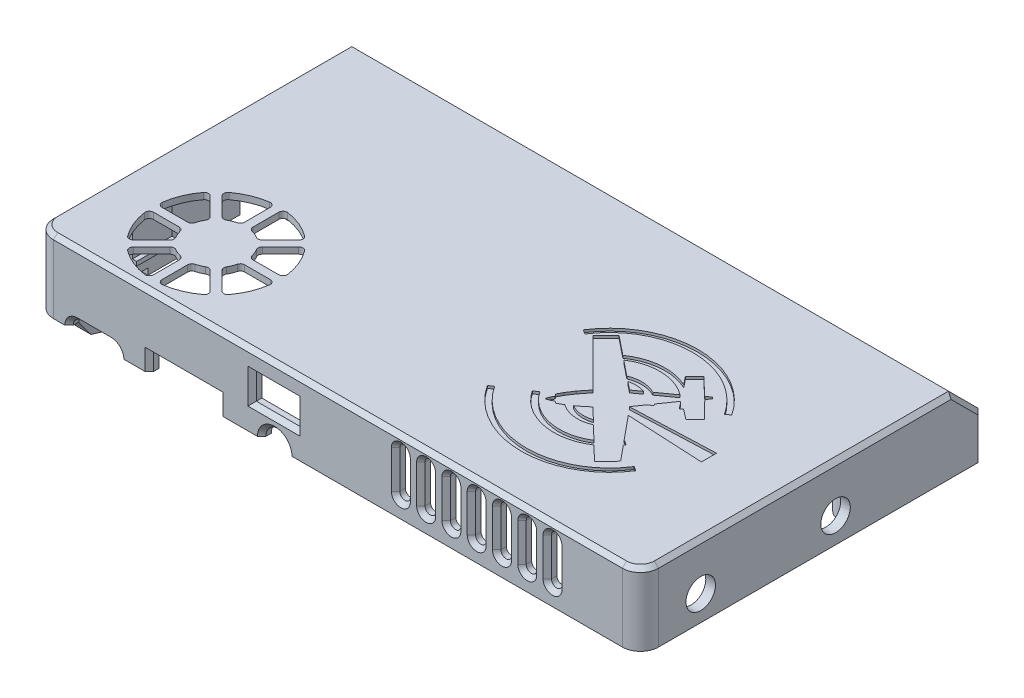
SolidWorks part; units mm, degrees
ref_plane "Front Plane" through (0, 0, 0) normal (0, 0, 1) x (1, 0, 0)
ref_plane "Top Plane" through (0, 0, 0) normal (0, 1, 0) x (1, 0, 0)
ref_plane "Right Plane" through (0, 0, 0) normal (1, 0, 0) x (0, 0, -1)
sketch "Sketch1" plane through (0, 0, 0) normal (0, 1, 0) x (1, 0, 0)
  line L0 (-71.5618, 12.356) -> (65.4382, 12.356) construction
  line L1 (-71.5618, 49.606) -> (65.4382, 49.606)
  line L2 (-71.5618, 49.606) -> (-71.5618, -24.894)
  line L3 (-71.5618, -24.894) -> (65.4382, -24.894)
  line L4 (65.4382, 49.606) -> (65.4382, -24.894)
  line L5 (-60.6618, -24.894) -> (-60.6618, -31.6828) construction
  line L6 (-68.0618, 27.606) -> (-10.0618, 27.606)
  line L7 (-68.0618, 27.606) -> (-68.0618, -21.394)
  line L8 (-68.0618, -21.394) -> (-10.0618, -21.394)
  line L9 (-10.0618, 27.606) -> (-10.0618, -21.394)
  line L10 (-39.5618, -24.894) -> (-39.5618, -31.6828) construction
  line L11 (-18.0618, -24.894) -> (-18.0618, -31.6828) construction
  line L12 (-65.4118, -26.5648) -> (-55.9118, -26.5648) construction
  line L13 (-48.0618, -26.5648) -> (-31.0618, -26.5648) construction
  line L14 (-22.0618, -26.5648) -> (-14.0618, -26.5648) construction
  line L15 (-72.5618, 9.606) -> (-72.5618, -3.394) construction
  line L16 (-71.5618, 12.356) -> (-72.5618, 12.356) construction
  line L17 (-60.6618, -24.894) -> (-60.6618, 40.2849) construction
  dimension "D1" = 137
  dimension "D2" = 74.5
  dimension "D3" = 49
  dimension "D4" = 58
  dimension "D5" = 3.5
  dimension "D6" = 3.5
  dimension "D7" = 10.9
  dimension "D8" = 32
  dimension "D9" = 53.5
  dimension "D10" = 2
  dimension "D11" = 13
  dimension "D12" = 9.5
  dimension "D13" = 17
  dimension "D14" = 8
sketch "Sketch3" plane through (0, 0, 0) normal (0, 1, 0) x (1, 0, 0)
  line L2 (-72.5618, -25.894) -> (66.4382, -25.894) construction
  line L3 (68.7382, -28.194) -> (68.7382, 52.906) construction
  line L4 (68.7382, 52.906) -> (-74.8618, 52.906)
  line L5 (-74.8618, 52.906) -> (-74.8618, -28.194)
  line L6 (-74.8618, -28.194) -> (68.7382, -28.194)
  line L8 (66.4382, 50.606) -> (-72.5618, 50.606)
  line L9 (66.4382, -25.894) -> (66.4382, 50.606)
  line L10 (-72.5618, -25.894) -> (66.4382, -25.894)
  line L11 (-72.5618, 50.606) -> (-72.5618, -25.894)
  line L12 (66.4382, 50.606) -> (-72.5618, 50.606)
  line L13 (66.4382, -25.894) -> (66.4382, 50.606)
  line L14 (-72.5618, -25.894) -> (66.4382, -25.894)
  line L15 (-72.5618, 50.606) -> (-72.5618, -25.894)
  line L16 (-3.0618, 12.356) -> (-3.0618, 52.906) construction
  line L17 (-71.5618, 12.356) -> (65.4382, 12.356) construction
  line L18 (66.4382, -25.894) -> (66.4382, 50.606) construction
  line L20 (-74.8618, 12.356) -> (52.7382, 12.356) construction
  line L22 (-74.8618, -28.194) -> (68.7382, -28.194) construction
  line L23 (68.7382, -28.194) -> (68.7382, 52.906)
  dimension "D1" = 1
  dimension "D2" = 2.3
extrude "Boss-Extrude1" add sketch "Sketch3" along normal blind 17.2
sketch "Sketch5" plane through (0, 0, 0) normal (0, 1, 0) x (1, 0, 0)
  line L1 (-72.5618, 50.606) -> (66.4382, 50.606)
  line L2 (-72.5618, 50.606) -> (-72.5618, -25.894)
  line L3 (-72.5618, -25.894) -> (66.4382, -25.894)
  line L4 (66.4382, 50.606) -> (66.4382, -25.894)
sketch "Sketch11" plane through (0, 0, 28.194) normal (0, 0, 1) x (1, 0, 0)
  line L0 (-74.8618, 17.2) -> (-74.8618, 0) construction
  line L2 (-66.8618, 0) -> (-54.8618, 0)
  line L3 (-66.8618, 0) -> (-66.8618, 2)
  line L4 (-66.8618, 2) -> (-54.8618, 2)
  line L5 (-54.8618, 0) -> (-54.8618, 2)
  line L9 (-47.8118, 4) -> (-31.3118, 4)
  line L10 (-47.8118, 4) -> (-47.8118, 0)
  line L11 (-47.8118, 0) -> (-31.3118, 0)
  line L12 (-31.3118, 4) -> (-31.3118, 0)
  line L14 (-39.5618, 0) -> (-39.528, 10.3) construction
  line L15 (-48.0618, 0) -> (-31.0618, 0) construction
  line L16 (-18.0618, 0) -> (-18.0618, 10.3) construction
  line L17 (-22.0618, 0) -> (-14.0618, 0) construction
  circle A0 centre (-18.0618, 0) radius 3.1
  dimension "D5" = 6.2
  dimension "D1" = 4
  dimension "D2" = 2
  dimension "D3" = 12
  dimension "D4" = 16.5
  dimension "D7" = 8
extrude "Cut-Extrude1" cut sketch "Sketch11" against normal up to next
sketch "Sketch14" plane through (0, 0, 0) normal (0, -1, 0) x (1, 0, 0)
  line L1 (-74.8618, 11.894) -> (-72.5618, 11.894)
  line L2 (-74.8618, 11.894) -> (-74.8618, -18.106)
  line L3 (-74.8618, -18.106) -> (-72.5618, -18.106)
  line L4 (-72.5618, 11.894) -> (-72.5618, -18.106)
  dimension "D1" = 30
extrude "Boss-Extrude6" add sketch "Sketch14" along normal blind 2.8
sketch "Sketch15" plane through (-74.8618, 0, 0) normal (-1, 0, 0) x (0, 0, 1)
  line L0 (11.894, -2.8) -> (-18.106, -2.8) construction
  line L1 (-9.7403, -2.8) -> (3.7597, -2.8)
  line L2 (-9.7403, -2.8) -> (-9.7403, -1.8)
  line L3 (-9.7403, -1.8) -> (3.7597, -1.8)
  line L4 (3.7597, -2.8) -> (3.7597, -1.8)
sketch "Sketch94" plane through (0, -2.8, 0) normal (0, -1, 0) x (1, 0, 0)
  line L0 (-74.8618, -9.7403) -> (-74.8618, 3.7597) construction
  line L1 (-72.5618, 3.7671) -> (-74.8618, 3.7671)
  line L2 (-72.5618, 3.7671) -> (-72.5618, -9.7403)
  line L3 (-72.5618, -9.7403) -> (-74.8618, -9.7403)
  line L4 (-74.8618, 3.7671) -> (-74.8618, -9.7403)
  line L5 (-74.8618, -30.106) -> (-74.8618, -9.7329) construction
extrude "Boss-Extrude11" add sketch "Sketch94" along normal blind 1.5
sketch "Sketch35" plane through (0, 17.2, 0) normal (0, 1, 0) x (1, 0, 0)
  line L1 (-72.5618, 50.606) -> (66.4382, 50.606)
  line L2 (-72.5618, 50.606) -> (-72.5618, -25.894)
  line L3 (-72.5618, -25.894) -> (66.4382, -25.894)
  line L4 (66.4382, 50.606) -> (66.4382, -25.894)
extrude "Boss-Extrude7" add sketch "Sketch35" against normal blind 2
sketch "Sketch36" plane through (0, 17.2, 0) normal (0, 1, 0) x (1, 0, 0)
  line L0 (24.1618, 0.3922) -> (23.0119, -0.3579)
  line L1 (34.6516, 0.4143) -> (35.8046, -0.3309)
  line L2 (24.1474, 7.2037) -> (22.9944, 7.949)
  line L3 (34.6373, 7.2258) -> (35.7871, 7.9759)
  line L4 (45.9489, -6.8877) -> (46.9923, -7.5622)
  line L5 (39.4174, -2.6661) -> (40.5245, -3.3816)
  line L6 (19.409, -2.7082) -> (18.305, -3.4284)
  line L7 (12.8953, -6.9573) -> (11.8548, -7.6361)
  line L8 (12.8501, 14.5058) -> (11.8067, 15.1802)
  line L9 (19.3816, 10.2841) -> (18.2746, 10.9997)
  line L10 (39.3901, 10.3263) -> (40.4941, 11.0465)
  line L11 (45.9037, 14.5754) -> (46.9443, 15.2542)
  line L12 (52.9704, 2.0329) -> (31.2725, 3.1101)
  line L13 (52.9704, 5.6235) -> (31.2725, 4.7515)
  line L14 (52.9704, 2.0329) -> (52.9704, 5.6235)
  line L15 (31.2725, 3.1101) -> (31.2725, 4.7515)
  arc A0 (46.9443, 15.2542) -> (11.8067, 15.1802) centre (29.3995, 3.809) ccw
  arc A1 (45.9037, 14.5754) -> (12.8501, 14.5058) centre (29.3995, 3.809) ccw
  arc A2 (34.6373, 7.2258) -> (24.1474, 7.2037) centre (29.3995, 3.809) ccw
  arc A3 (35.7871, 7.9759) -> (22.9944, 7.949) centre (29.3995, 3.809) ccw
  arc A4 (40.4941, 11.0465) -> (18.2746, 10.9997) centre (29.3995, 3.809) ccw
  arc A5 (39.3901, 10.3263) -> (19.3816, 10.2841) centre (29.3995, 3.809) ccw
  arc A6 (11.8548, -7.6361) -> (46.9923, -7.5622) centre (29.3995, 3.809) ccw
  arc A7 (12.8953, -6.9573) -> (45.9489, -6.8877) centre (29.3995, 3.809) ccw
  arc A8 (18.305, -3.4284) -> (40.5245, -3.3816) centre (29.3995, 3.809) ccw
  arc A9 (19.409, -2.7082) -> (39.4174, -2.6661) centre (29.3995, 3.809) ccw
  arc A10 (23.0119, -0.3579) -> (35.8046, -0.3309) centre (29.3995, 3.809) ccw
  arc A11 (24.1618, 0.3922) -> (34.6516, 0.4143) centre (29.3995, 3.809) ccw
extrude "Cut-Extrude4" cut sketch "Sketch36" against normal blind 0.6
sketch "Sketch37" plane through (0, 17.2, 0) normal (0, 1, 0) x (1, 0, 0)
  line L0 (28.805, 0.4761) -> (40.1826, -10.5566)
  line L1 (40.1826, -10.5566) -> (43.2384, -7.4053)
  line L2 (43.2384, -7.4053) -> (33.0944, 4.8995)
  line L3 (33.0944, 4.8995) -> (38.1664, 12.1985)
  line L4 (38.1664, 12.1985) -> (42.4176, 8.9024)
  line L5 (42.4176, 8.9024) -> (44.5689, 11.121)
  line L6 (44.5689, 11.121) -> (40.5449, 15.2662)
  line L7 (40.5449, 15.2662) -> (41.3442, 16.2971)
  line L8 (41.3442, 16.2971) -> (41.1146, 16.4751)
  line L9 (28.805, 0.4761) -> (26.7077, -1.2529)
  line L10 (26.7077, -1.2529) -> (24.9219, -2.47)
  line L11 (24.9219, -2.47) -> (23.6139, -3.1724)
  line L12 (23.6139, -3.1724) -> (23.1085, -2.8212)
  line L13 (23.1085, -2.8212) -> (22.3443, -3.2316)
  line L14 (22.3443, -3.2316) -> (21.6545, -3.4615)
  line L15 (21.6545, -3.4615) -> (21.4618, -3.4615)
  line L16 (41.1146, 16.4751) -> (21.4618, -3.4615) construction
  line L17 (21.459, -3.2688) -> (21.4618, -3.4615)
  line L18 (21.6791, -2.5758) -> (21.459, -3.2688)
  line L19 (22.0784, -1.8058) -> (21.6791, -2.5758)
  line L20 (21.72, -1.3055) -> (22.0784, -1.8058)
  line L21 (22.4036, 0.0124) -> (21.72, -1.3055)
  line L22 (23.595, 1.8155) -> (22.4036, 0.0124)
  line L23 (25.2938, 3.9374) -> (23.595, 1.8155)
  line L24 (40.9334, 16.7021) -> (41.1146, 16.4751)
  line L25 (39.9141, 15.8881) -> (40.9334, 16.7021)
  line L26 (35.7115, 19.8523) -> (39.9141, 15.8881)
  line L27 (33.524, 17.6694) -> (35.7115, 19.8523)
  line L28 (36.8807, 13.4659) -> (33.524, 17.6694)
  line L29 (29.6552, 8.2897) -> (36.8807, 13.4659)
  line L30 (17.2062, 18.2563) -> (29.6552, 8.2897)
  line L31 (14.099, 15.1556) -> (17.2062, 18.2563)
  line L32 (25.2938, 3.9374) -> (14.099, 15.1556)
extrude "Cut-Extrude5" cut sketch "Sketch37" against normal blind 0.6
sketch "Sketch48" plane through (0, 17.2, 0) normal (0, 1, 0) x (1, 0, 0)
  line L0 (-14.9618, -28.194) -> (68.7382, -28.194) construction
  line L2 (-74.8618, 12.356) -> (-35.5735, 12.356) construction
  line L3 (-74.8618, 52.906) -> (-74.8618, -28.194) construction
  line L4 (68.7382, -28.194) -> (68.7382, 52.906) construction
  circle A0 centre (64.4382, 27.806) radius 4.3
  circle A3 centre (64.4382, -23.894) radius 4.3
  dimension "D1" = 4.3
  dimension "D2" = 56
extrude "Boss-Extrude9" add sketch "Sketch48" against normal up to vertex
sketch "Sketch87" plane through (0, 15.2, 0) normal (0, -1, 0) x (1, 0, 0)
  line L0 (-68.0618, -24.606) -> (-72.5618, -24.606)
  line L1 (-72.5618, -50.606) -> (-72.5618, -18.106) construction
  line L2 (-72.5618, -24.606) -> (-72.5618, -30.606)
  line L3 (-13.0618, -27.606) -> (-13.0618, -30.606)
  line L4 (-65.0618, -30.606) -> (-72.5618, -30.606)
  line L6 (-13.0618, -30.606) -> (-7.0618, -30.606)
  line L7 (-7.0618, -30.606) -> (-7.0618, -27.606)
  line L8 (-13.0618, 21.394) -> (-13.0618, 25.894)
  line L9 (-66.8618, 25.894) -> (-65.1415, 22.0812)
  line L10 (-68.0618, 18.394) -> (-72.5618, 18.394)
  line L11 (-72.5618, 11.894) -> (-72.5618, 25.894) construction
  line L12 (-72.5618, 18.394) -> (-72.5618, 25.894)
  line L13 (-72.5618, 25.894) -> (-66.8618, 25.894)
  line L14 (-65.0618, -27.606) -> (-65.0618, -30.606)
  line L16 (9.9382, 25.894) -> (-54.8618, 25.894) construction
  line L17 (-13.0618, 25.894) -> (-7.0618, 25.894)
  line L18 (-7.0618, 25.894) -> (-7.0618, 21.394)
  arc A0 (-68.0618, 18.394) -> (-65.6141, 23.1287) centre (-68.0618, 21.394) ccw
  arc A1 (-65.0618, -27.606) -> (-68.0618, -24.606) centre (-68.0618, -27.606) ccw
  arc A2 (-13.0618, 21.394) -> (-7.0618, 21.394) centre (-10.0618, 21.394) ccw
  arc A3 (-7.0618, -27.606) -> (-13.0618, -27.606) centre (-10.0618, -27.606) ccw
  arc A4 (-7.0618, -27.606) -> (-13.0618, -27.606) centre (-10.0618, -27.606) ccw
extrude "Boss-Extrude10" add sketch "Sketch87" along normal offset from surface (18.3 mm away) 3.1
fillet "Fillet15" radius 4.3 2 edges at (68.7382, 8.6, 28.194) (-74.8618, 8.6, 28.194)
sketch "Sketch68" plane through (68.7382, 0, 0) normal (1, 0, 0) x (0, 0, -1)
  line L0 (18.106, 6) -> (-13.894, 6) construction
  line L1 (-23.894, 17.2) -> (-23.894, 0) construction
  line L4 (-23.894, 0) -> (52.906, 0) construction
  circle A0 centre (-13.894, 6) radius 3.5
  circle A1 centre (18.106, 6) radius 3.5
  dimension "D1" = 32
  dimension "D2" = 10
  dimension "D3" = 6
extrude "Cut-Extrude19" cut sketch "Sketch68" against normal up to next
sketch "Sketch81" plane through (0, 0, 28.194) normal (0, 0, 1) x (1, 0, 0)
  line L0 (47.876, 4.6038) -> (47.876, 13.6038) construction
  line L1 (46.626, 4.6038) -> (46.626, 13.6038)
  line L2 (49.126, 4.6038) -> (49.126, 13.6038)
  line L3 (41.876, 4.6038) -> (41.876, 13.6038) construction
  line L4 (40.626, 4.6038) -> (40.626, 13.6038)
  line L5 (43.126, 4.6038) -> (43.126, 13.6038)
  line L6 (35.876, 4.6038) -> (35.876, 13.6038) construction
  line L7 (34.626, 4.6038) -> (34.626, 13.6038)
  line L8 (37.126, 4.6038) -> (37.126, 13.6038)
  line L9 (29.876, 4.6038) -> (29.876, 13.6038) construction
  line L10 (28.626, 4.6038) -> (28.626, 13.6038)
  line L11 (31.126, 4.6038) -> (31.126, 13.6038)
  line L12 (23.876, 4.6038) -> (23.876, 13.6038) construction
  line L13 (22.626, 4.6038) -> (22.626, 13.6038)
  line L14 (25.126, 4.6038) -> (25.126, 13.6038)
  line L15 (17.876, 4.6038) -> (17.876, 13.6038) construction
  line L16 (16.626, 4.6038) -> (16.626, 13.6038)
  line L17 (19.126, 4.6038) -> (19.126, 13.6038)
  line L18 (11.876, 4.6038) -> (11.876, 13.6038) construction
  line L19 (10.626, 4.6038) -> (10.626, 13.6038)
  line L20 (13.126, 4.6038) -> (13.126, 13.6038)
  arc A0 (46.626, 4.6038) -> (49.126, 4.6038) centre (47.876, 4.6038) ccw
  arc A1 (49.126, 13.6038) -> (46.626, 13.6038) centre (47.876, 13.6038) ccw
  arc A2 (40.626, 4.6038) -> (43.126, 4.6038) centre (41.876, 4.6038) ccw
  arc A3 (43.126, 13.6038) -> (40.626, 13.6038) centre (41.876, 13.6038) ccw
  arc A4 (34.626, 4.6038) -> (37.126, 4.6038) centre (35.876, 4.6038) ccw
  arc A5 (37.126, 13.6038) -> (34.626, 13.6038) centre (35.876, 13.6038) ccw
  arc A6 (28.626, 4.6038) -> (31.126, 4.6038) centre (29.876, 4.6038) ccw
  arc A7 (31.126, 13.6038) -> (28.626, 13.6038) centre (29.876, 13.6038) ccw
  arc A8 (22.626, 4.6038) -> (25.126, 4.6038) centre (23.876, 4.6038) ccw
  arc A9 (25.126, 13.6038) -> (22.626, 13.6038) centre (23.876, 13.6038) ccw
  arc A10 (16.626, 4.6038) -> (19.126, 4.6038) centre (17.876, 4.6038) ccw
  arc A11 (19.126, 13.6038) -> (16.626, 13.6038) centre (17.876, 13.6038) ccw
  arc A12 (10.626, 4.6038) -> (13.126, 4.6038) centre (11.876, 4.6038) ccw
  arc A13 (13.126, 13.6038) -> (10.626, 13.6038) centre (11.876, 13.6038) ccw
  point P2 (47.876, 9.1038)
  point P11 (41.876, 9.1038)
  point P18 (35.876, 9.1038)
  point P25 (29.876, 9.1038)
  point P32 (23.876, 9.1038)
  point P39 (17.876, 9.1038)
  point P44 (11.876, 9.1038)
  dimension "D1" = 7
extrude "Cut-Extrude20" cut sketch "Sketch81" against normal up to surface (2.3 mm away) up to face at (-38.6618, 3.7917, 25.894)
fillet "Fillet24" radius 2 1 edges at (60.6317, 7.6, 25.894)
fillet "Fillet25" radius 2 1 edges at (-54.8618, 2, 27.044)
fillet "Fillet26" radius 2 1 edges at (-66.8618, 2, 27.044)
chamfer "Chamfer1" distance 1 angle 45 7 edges at (-18.0618, 3.1, 28.194) (-31.3118, 2, 28.194) (-39.5618, 4, 28.194) (-47.8118, 2, 28.194) (-55.4476, 1.4142, 28.194) (-60.8618, 2, 28.194) (-66.276, 1.4142, 28.194)
fillet "Fillet51" radius 3 1 edges at (-72.5618, -1.55, 25.894)
chamfer "Chamfer3" distance 2 angle 56 5 edges at (-68.2118, -3.1, 25.894) (-71.6831, -3.1, 25.0153) (-72.5618, -3.1, 20.644) (-72.5618, -3.1, -27.606) (-10.0618, -3.1, 25.894)
hole_wizard "Ø2.3 (2.3) Diameter Hole2" positions "Sketch91" profile "Sketch90" hole size "Ø2.3" standard "ANSI Metric"
sketch "Sketch91" plane through (0, 0, 0) normal (0, -1, 0) x (-1, 0, 0)
  point P0 (-64.4382, -23.894)
  point P7 (-64.4382, 27.806)
sketch "Sketch90" plane through (64.4382, 0, 23.894) normal (1, 0, 0) x (0, 0, -1)
  line L0 (0, 0) -> (0, 12)
  line L1 (0, 12) -> (1.15, 12)
  line L2 (1.15, 12) -> (1.15, 0)
  line L5 (1.15, 0) -> (0, 0)
  line L10 (0, 12) -> (-1.15, 12) construction
  line L11 (0, -6.35) -> (0, 107.95) construction
  dimension "Hole Dia." = 2.3
  dimension "Hole Depth" = 12
  dimension "Drill Angle" = 180
hole_wizard "Ø2.3 (2.3) Diameter Hole1" positions "Sketch93" profile "Sketch92" hole size "Ø2.3" standard "ANSI Metric"
sketch "Sketch93" plane through (0, -3.1, 0) normal (0, -1, 0) x (-1, 0, 0)
  point P0 (68.0618, -21.394)
  point P4 (68.0618, 27.606)
  point P7 (10.0618, 27.606)
  point P11 (10.0618, -21.394)
sketch "Sketch92" plane through (-68.0618, -3.1, 21.394) normal (1, 0, 0) x (0, 0, -1)
  line L0 (0, 0) -> (0, 13)
  line L1 (0, 13) -> (1.15, 13)
  line L2 (1.15, 13) -> (1.15, 0)
  line L5 (1.15, 0) -> (0, 0)
  line L10 (0, 13) -> (-1.15, 13) construction
  line L11 (0, -6.35) -> (0, 107.95) construction
  dimension "Hole Dia." = 2.3
  dimension "Hole Depth" = 13
  dimension "Drill Angle" = 180
chamfer "Chamfer4" distance 1 angle 45 1 edges at (-74.8618, -4.3, -2.9866)
sketch "Sketch95" plane through (-74.8618, 0, 0) normal (-1, 0, 0) x (0, 0, 1)
  line L0 (-18.606, 14.2331) -> (-18.606, 8.1669) construction
  line L1 (-25.5774, 11.2) -> (-11.6346, 11.2) construction
  line L2 (-24.606, -3.1) -> (-30.606, -3.1) construction
  line L3 (-24.606, -0.1349) -> (-24.606, -3.1) construction
  line L7 (-23.606, 13.2) -> (-13.606, 13.2)
  line L8 (-23.606, 13.2) -> (-23.606, 9.2)
  line L9 (-23.606, 9.2) -> (-13.606, 9.2)
  line L10 (-13.606, 13.2) -> (-13.606, 9.2)
  line L11 (-23.606, 13.2) -> (-13.606, 9.2) construction
  line L12 (-23.606, 9.2) -> (-13.606, 13.2) construction
  point P6 (-18.606, 11.2)
  dimension "D1" = 14.3
  dimension "D2" = 6
  dimension "D3" = 10
  dimension "D4" = 4
extrude "Cut-Extrude21" cut sketch "Sketch95" against normal up to next
fillet "Fillet52" radius 1 4 edges at (-73.7118, 9.2, -23.606) (-73.7118, 9.2, -13.606) (-73.7118, 13.2, -13.606) (-73.7118, 13.2, -23.606)
chamfer "Chamfer5" distance 1 angle 45 8 edges at (-74.8618, 13.2, -18.606) (-74.8618, 12.9071, -23.3131) (-74.8618, 12.9071, -13.8989) (-74.8618, 11.2, -23.606) (-74.8618, 11.2, -13.606) (-74.8618, 9.4929, -23.3131) (-74.8618, 9.4929, -13.8989) (-74.8618, 9.2, -18.606)
sketch "Sketch96" plane through (0, 15.2, 0) normal (0, -1, 0) x (1, 0, 0)
  line L0 (-31.3118, 25.894) -> (-47.8118, 25.894) construction
  line L1 (-64.7549, -4.606) -> (-34.2549, -4.606)
  line L2 (-64.7549, -4.606) -> (-64.7549, 25.894)
  line L3 (-64.7549, 25.894) -> (-34.2549, 25.894)
  line L4 (-34.2549, -4.606) -> (-34.2549, 25.894)
  dimension "D1" = 30.5
  dimension "D2" = 30.5
extrude "Cut-Extrude22" cut sketch "Sketch96" against normal blind 0.5
sketch "Sketch97" plane through (0, 15.7, 0) normal (0, -1, 0) x (1, 0, 0)
  line L1 (-48.5049, 18.39) -> (-48.5049, 24.5004)
  line L2 (-50.5049, 18.39) -> (-50.5049, 24.5004)
  line L5 (-43.3206, 15.4141) -> (-38.9999, 19.7349)
  line L6 (-44.7348, 16.8283) -> (-40.4141, 21.1491)
  line L7 (-41.759, 9.644) -> (-35.6485, 9.644)
  line L8 (-41.759, 11.644) -> (-35.6485, 11.644)
  line L9 (-44.7348, 4.4597) -> (-40.4141, 0.1389)
  line L10 (-43.3206, 5.8739) -> (-38.9999, 1.5532)
  line L11 (-50.5049, 2.898) -> (-50.5049, -3.2124)
  line L12 (-48.5049, 2.898) -> (-48.5049, -3.2124)
  line L13 (-55.6893, 5.8739) -> (-60.01, 1.5532)
  line L14 (-54.275, 4.4597) -> (-58.5958, 0.1389)
  line L15 (-57.2509, 11.644) -> (-63.3613, 11.644)
  line L16 (-57.2509, 9.644) -> (-63.3613, 9.644)
  line L17 (-54.275, 16.8283) -> (-58.5958, 21.1491)
  line L18 (-55.6893, 15.4141) -> (-60.01, 19.7349)
  arc A0 (-61.518, 19.6266) -> (-64.3511, 12.7869) centre (-49.5049, 10.644) ccw
  arc A1 (-55.5349, 14.1991) -> (-56.2826, 12.394) centre (-49.5049, 10.644) ccw
  arc A2 (-56.2826, 8.894) -> (-55.5349, 7.0889) centre (-49.5049, 10.644) ccw
  arc A3 (-64.3511, 8.5011) -> (-61.518, 1.6614) centre (-49.5049, 10.644) ccw
  arc A4 (-58.4875, -1.369) -> (-51.6478, -4.2021) centre (-49.5049, 10.644) ccw
  arc A5 (-53.0601, 4.614) -> (-51.2549, 3.8663) centre (-49.5049, 10.644) ccw
  arc A6 (-47.7549, 3.8663) -> (-45.9498, 4.614) centre (-49.5049, 10.644) ccw
  arc A7 (-47.3621, -4.2021) -> (-40.5223, -1.369) centre (-49.5049, 10.644) ccw
  arc A8 (-37.4919, 1.6614) -> (-34.6588, 8.5011) centre (-49.5049, 10.644) ccw
  arc A9 (-43.4749, 7.0889) -> (-42.7272, 8.894) centre (-49.5049, 10.644) ccw
  arc A10 (-42.7272, 12.394) -> (-43.4749, 14.1991) centre (-49.5049, 10.644) ccw
  arc A11 (-34.6588, 12.7869) -> (-37.4919, 19.6266) centre (-49.5049, 10.644) ccw
  arc A12 (-40.5223, 22.657) -> (-47.3621, 25.4902) centre (-49.5049, 10.644) ccw
  arc A13 (-45.9498, 16.674) -> (-47.7549, 17.4217) centre (-49.5049, 10.644) ccw
  arc A14 (-51.2549, 17.4217) -> (-53.0601, 16.674) centre (-49.5049, 10.644) ccw
  arc A15 (-51.6478, 25.4902) -> (-58.4875, 22.657) centre (-49.5049, 10.644) ccw
  arc A16 (-56.2826, 8.894) -> (-57.2509, 9.644) centre (-57.2509, 8.644) ccw
  arc A17 (-64.3511, 8.5011) -> (-63.3613, 9.644) centre (-63.3613, 8.644) cw
  arc A18 (-61.518, 1.6614) -> (-60.01, 1.5532) centre (-60.7171, 2.2603) ccw
  arc A19 (-55.6893, 5.8739) -> (-55.5349, 7.0889) centre (-56.3964, 6.581) ccw
  arc A20 (-50.5049, 2.898) -> (-51.2549, 3.8663) centre (-51.5049, 2.898) ccw
  arc A21 (-54.275, 4.4597) -> (-53.0601, 4.614) centre (-53.5679, 3.7526) cw
  arc A22 (-58.4875, -1.369) -> (-58.5958, 0.1389) centre (-57.8887, -0.5682) cw
  arc A23 (-51.6478, -4.2021) -> (-50.5049, -3.2124) centre (-51.5049, -3.2124) ccw
  arc A24 (-47.3621, -4.2021) -> (-48.5049, -3.2124) centre (-47.5049, -3.2124) cw
  arc A25 (-40.5223, -1.369) -> (-40.4141, 0.1389) centre (-41.1212, -0.5682) ccw
  arc A26 (-47.7549, 3.8663) -> (-48.5049, 2.898) centre (-47.5049, 2.898) ccw
  arc A27 (-44.7348, 4.4597) -> (-45.9498, 4.614) centre (-45.4419, 3.7526) ccw
  arc A28 (-38.9999, 1.5532) -> (-37.4919, 1.6614) centre (-38.2928, 2.2603) ccw
  arc A29 (-43.3206, 5.8739) -> (-43.4749, 7.0889) centre (-42.6135, 6.581) cw
  arc A30 (-41.759, 9.644) -> (-42.7272, 8.894) centre (-41.759, 8.644) ccw
  arc A31 (-34.6588, 8.5011) -> (-35.6485, 9.644) centre (-35.6485, 8.644) ccw
  arc A32 (-35.6485, 11.644) -> (-34.6588, 12.7869) centre (-35.6485, 12.644) ccw
  arc A33 (-42.7272, 12.394) -> (-41.759, 11.644) centre (-41.759, 12.644) ccw
  arc A34 (-43.4749, 14.1991) -> (-43.3206, 15.4141) centre (-42.6135, 14.707) cw
  arc A35 (-37.4919, 19.6266) -> (-38.9999, 19.7349) centre (-38.2928, 19.0278) ccw
  arc A36 (-40.4141, 21.1491) -> (-40.5223, 22.657) centre (-41.1212, 21.8562) ccw
  arc A37 (-44.7348, 16.8283) -> (-45.9498, 16.674) centre (-45.4419, 17.5354) cw
  arc A38 (-47.7549, 17.4217) -> (-48.5049, 18.39) centre (-47.5049, 18.39) cw
  arc A39 (-48.5049, 24.5004) -> (-47.3621, 25.4902) centre (-47.5049, 24.5004) cw
  arc A40 (-50.5049, 24.5004) -> (-51.6478, 25.4902) centre (-51.5049, 24.5004) ccw
  arc A41 (-51.2549, 17.4217) -> (-50.5049, 18.39) centre (-51.5049, 18.39) ccw
  arc A42 (-53.0601, 16.674) -> (-54.275, 16.8283) centre (-53.5679, 17.5354) cw
  arc A43 (-58.5958, 21.1491) -> (-58.4875, 22.657) centre (-57.8887, 21.8562) cw
  arc A44 (-60.01, 19.7349) -> (-61.518, 19.6266) centre (-60.7171, 19.0278) ccw
  arc A45 (-55.5349, 14.1991) -> (-55.6893, 15.4141) centre (-56.3964, 14.707) ccw
  arc A46 (-57.2509, 11.644) -> (-56.2826, 12.394) centre (-57.2509, 12.644) ccw
  arc A47 (-63.3613, 11.644) -> (-64.3511, 12.7869) centre (-63.3613, 12.644) cw
  point P43 (-49.5049, 10.644)
  point P80 (-48.5049, 17.5722)
  point P83 (-48.5049, 25.6106)
  point P86 (-50.5049, 25.6106)
  point P89 (-50.5049, 17.5722)
  dimension "D1" = 1
  dimension "D3" = 8
extrude "Cut-Extrude23" cut sketch "Sketch97" against normal up to next
sketch "Sketch98" plane through (0, 15.2, 0) normal (0, -1, 0) x (1, 0, 0)
  line L0 (-64.7549, 25.894) -> (-64.7549, -4.606) construction
  line L1 (-64.7549, 15.2653) -> (-66.7549, 15.2653)
  line L2 (-64.7549, 15.2653) -> (-64.7549, 5.8822)
  line L3 (-64.7549, 5.8822) -> (-66.7549, 5.8822)
  line L4 (-66.7549, 15.2653) -> (-66.7549, 5.8822)
  line L5 (-32.2549, 15.3356) -> (-34.2549, 15.3356)
  line L6 (-32.2549, 5.9524) -> (-34.2549, 5.9524)
  line L7 (-32.2549, 15.3356) -> (-32.2549, 5.9524)
  line L8 (-34.2549, 15.3356) -> (-34.2549, 5.9524)
  dimension "D1" = 2
  dimension "D2" = 2
extrude "Boss-Extrude12" add sketch "Sketch98" along normal blind 7.5
sketch "Sketch100" plane through (-64.7549, 0, 0) normal (1, 0, 0) x (0, 0, -1)
  line L0 (-5.8822, 7.7) -> (-5.8822, 15.2) construction
  line L1 (-15.2653, 7.7) -> (-5.8822, 7.7)
  line L2 (-15.2653, 7.7) -> (-15.2653, 8.7)
  line L3 (-15.2653, 8.7) -> (-5.8822, 8.7)
  line L4 (-5.8822, 7.7) -> (-5.8822, 8.7)
  dimension "D1" = 1
extrude "Boss-Extrude13" add sketch "Sketch100" along normal blind 1
sketch "Sketch101" plane through (-34.2549, 0, 0) normal (-1, 0, 0) x (0, 0, 1)
  line L0 (5.9524, 7.7) -> (5.9524, 15.2) construction
  line L1 (15.3356, 7.7) -> (5.9524, 7.7)
  line L2 (15.3356, 7.7) -> (15.3356, 8.7)
  line L3 (15.3356, 8.7) -> (5.9524, 8.7)
  line L4 (5.9524, 7.7) -> (5.9524, 8.7)
  dimension "D1" = 1
extrude "Boss-Extrude14" add sketch "Sketch101" along normal blind 1
sketch "Sketch103" plane through (0, 15.2, 0) normal (0, -1, 0) x (1, 0, 0)
  line L0 (66.4382, 20.0874) -> (66.4382, -23.9994) construction
  line L1 (-72.5618, -30.606) -> (66.4382, -30.606)
  line L2 (-72.5618, -30.606) -> (-72.5618, -32.106)
  line L3 (-72.5618, -32.106) -> (66.4382, -32.106)
  line L4 (66.4382, -30.606) -> (66.4382, -32.106)
  dimension "D1" = 1.5
extrude "Boss-Extrude24" add sketch "Sketch103" along normal up to surface (15.2 mm away) up to face at (-71.063, 0, 22.5852)
chamfer "Chamfer6" distance 1 angle 45 28 edges at (49.126, 9.1038, 28.194) (47.876, 14.8538, 28.194) (47.876, 3.3538, 28.194) (46.626, 9.1038, 28.194) (43.126, 9.1038, 28.194) (41.876, 14.8538, 28.194) (41.876, 3.3538, 28.194) (40.626, 9.1038, 28.194) (37.126, 9.1038, 28.194) (35.876, 14.8538, 28.194) (35.876, 3.3538, 28.194) (34.626, 9.1038, 28.194) (31.126, 9.1038, 28.194) (29.876, 14.8538, 28.194) (29.876, 3.3538, 28.194) (28.626, 9.1038, 28.194) (25.126, 9.1038, 28.194) (23.876, 14.8538, 28.194) (23.876, 3.3538, 28.194) (22.626, 9.1038, 28.194) (19.126, 9.1038, 28.194) (17.876, 14.8538, 28.194) (17.876, 3.3538, 28.194) (16.626, 9.1038, 28.194) (13.126, 9.1038, 28.194) (11.876, 14.8538, 28.194) (11.876, 3.3538, 28.194) (10.626, 9.1038, 28.194)
chamfer "Chamfer7" distance 1 angle 45 5 edges at (68.7382, 17.2, -14.506) (67.4788, 17.2, 26.9346) (-3.0618, 17.2, 28.194) (-73.6023, 17.2, 26.9346) (-74.8618, 17.2, -14.506)
sketch "Sketch105" plane through (0, 0, 0) normal (0, -1, 0) x (1, 0, 0)
  line L0 (-3.0618, -32.106) -> (-3.0618, -50.606) construction
  line L1 (-72.5618, -32.106) -> (66.4382, -32.106) construction
  line L3 (-4.0618, -32.106) -> (-4.0618, -50.606)
  line L4 (-2.0618, -32.106) -> (-2.0618, -50.606)
  line L5 (-4.0618, -32.106) -> (-2.0618, -32.106)
  line L6 (-4.0618, -50.606) -> (-2.0618, -50.606)
  dimension "D1" = 1
  dimension "D2" = 1
extrude "Boss-Extrude25" add sketch "Sketch105" against normal up to surface (15.2 mm away) up to face at (-3.0618, 15.2, -41.356)
sketch "Sketch106" plane through (0, 0, 0) normal (0, -1, 0) x (1, 0, 0)
  line L0 (-72.5618, -32.106) -> (-4.0618, -32.106) construction
  line L1 (-71.189, -32.106) -> (-70.189, -32.106)
  line L2 (-71.189, -32.106) -> (-71.189, -50.606)
  line L3 (-71.189, -50.606) -> (-70.189, -50.606)
  line L4 (-70.189, -32.106) -> (-70.189, -50.606)
  line L5 (-4.0618, -50.606) -> (-72.5618, -50.606) construction
  line L7 (-70.189, -38.0184) -> (-69.0618, -38.0184)
  line L8 (-70.189, -38.0184) -> (-70.189, -44.6936)
  line L9 (-70.189, -44.6936) -> (-69.0618, -44.6936)
  line L10 (-69.0618, -38.0184) -> (-69.0618, -44.6936)
  line L11 (-4.0618, -32.106) -> (-4.0618, -50.606) construction
  line L12 (-3.0618, -52.906) -> (-3.0618, -32.106) construction
  line L13 (68.7382, -52.906) -> (-74.8618, -52.906) construction
  line L14 (62.9382, -38.0184) -> (62.9382, -44.6936)
  line L15 (64.0655, -44.6936) -> (62.9382, -44.6936)
  line L16 (64.0655, -38.0184) -> (64.0655, -44.6936)
  line L17 (64.0655, -38.0184) -> (62.9382, -38.0184)
  line L18 (64.0655, -32.106) -> (64.0655, -50.606)
  line L19 (65.0655, -50.606) -> (64.0655, -50.606)
  line L20 (65.0655, -32.106) -> (65.0655, -50.606)
  line L21 (65.0655, -32.106) -> (64.0655, -32.106)
  line M7 (66.4382, -50.606) -> (-2.0618, -50.606)
  line M9 (-2.0618, -32.106) -> (66.4382, -32.106)
  dimension "D1" = 1
  dimension "D2" = 65
extrude "Boss-Extrude26" add sketch "Sketch106" against normal blind 8 contours L20 L18 L16 M9 M7 | L16 L17 L14 L15 | L10 L9 L8 L7 | L2 L3 L4 L1
sketch "Sketch107" plane through (-69.0618, 0, 0) normal (1, 0, 0) x (0, 0, -1)
  line L1 (38.0184, 0) -> (44.6936, 0)
  line L2 (38.0184, 0) -> (38.0184, 8)
  line L3 (38.0184, 8) -> (44.6936, 8)
  line L4 (44.6936, 0) -> (44.6936, 8)
  circle A0 centre (41.356, 4) radius 3.3376
  line M1 (38.0184, 0) -> (44.6936, 0)
  line M2 (44.6936, 0) -> (44.6936, 8)
  line M3 (44.6936, 8) -> (38.0184, 8)
  line M4 (38.0184, 8) -> (38.0184, 0)
extrude "Cut-Extrude24" cut sketch "Sketch107" against normal up to surface (1.1272 mm away) contours A0 L2 M1 M2 | A0 L4 M3 M4 up to face at (-70.189, 5, -33.5841)
sketch "Sketch108" plane through (62.9382, 0, 0) normal (-1, 0, 0) x (0, 0, 1)
  line L1 (-38.0184, 0) -> (-44.6936, 0)
  line L2 (-38.0184, 0) -> (-38.0184, 8)
  line L3 (-38.0184, 8) -> (-44.6936, 8)
  line L4 (-44.6936, 0) -> (-44.6936, 8)
  circle A0 centre (-41.356, 4) radius 3.3376
  line M1 (-44.6936, 0) -> (-38.0184, 0)
  line M2 (-38.0184, 0) -> (-38.0184, 8)
  line M3 (-38.0184, 8) -> (-44.6936, 8)
  line M4 (-44.6936, 8) -> (-44.6936, 0)
extrude "Cut-Extrude25" cut sketch "Sketch108" against normal up to surface (1.1272 mm away) contours A0 L4 M1 M2 | A0 L2 M3 M4 up to face at (64.0655, 4, -47.6498)
sketch "Sketch109" plane through (0, 0, 0) normal (0, -1, 0) x (1, 0, 0)
  line L1 (-77.5251, 31.2411) -> (75.2448, 31.2411)
  line L2 (-77.5251, 31.2411) -> (-77.5251, -30.7316)
  line L3 (-77.5251, -30.7316) -> (75.2448, -30.7316)
  line L4 (75.2448, 31.2411) -> (75.2448, -30.7316)
chamfer "Chamfer8" distance 7 angle 45 1 edges at (-3.0618, 17.2, -52.906)
chamfer "Chamfer9" distance 6 angle 45 2 edges at (32.1882, 15.2, -50.606) (-38.3118, 15.2, -50.606)
sketch "Sketch115" plane through (0, 15.2, 0) normal (0, -1, 0) x (1, 0, 0)
  line L0 (-18.2426, 15.194) -> (-18.2426, 10.194) construction
  line L1 (-24.7426, 15.194) -> (-11.7426, 15.194)
  line L2 (-24.7426, 15.194) -> (-24.7426, 10.194)
  line L3 (-24.7426, 10.194) -> (-11.7426, 10.194)
  line L4 (-11.7426, 15.194) -> (-11.7426, 10.194)
  line L6 (-30.3118, 28.194) -> (-22.1618, 28.194) construction
  dimension "D1" = 13
  dimension "D2" = 5
  dimension "D3" = 13
extrude "Boss-Extrude27" add sketch "Sketch115" along normal blind 12
sketch "Sketch116" plane through (0, 0, 10.194) normal (0, 0, -1) x (-1, 0, 0)
  circle A0 centre (18.2426, 9.2) radius 3.1
extrude "Cut-Extrude29" cut sketch "Sketch116" against normal through all
sketch "Sketch117" plane through (0, 0, 25.894) normal (0, 0, -1) x (-1, 0, 0)
  line L0 (13.0618, 0) -> (13.0618, 15.2) construction
  line L1 (23.4235, 12.3) -> (13.0618, 12.3)
  line L2 (23.4235, 12.3) -> (23.4235, 6.1)
  line L3 (23.4235, 6.1) -> (13.0618, 6.1)
  line L4 (13.0618, 12.3) -> (13.0618, 6.1)
  line L5 (23.4235, 12.3) -> (13.0618, 6.1) construction
  line L6 (23.4235, 6.1) -> (13.0618, 12.3) construction
  point P0 (18.2426, 9.2)
extrude "Cut-Extrude30" cut sketch "Sketch117" against normal up to next (2.3 mm away)
chamfer "Chamfer10" distance 1 angle 45 4 edges at (-18.2426, 6.1, 28.194) (-23.4235, 9.2, 28.194) (-18.2426, 12.3, 28.194) (-13.0618, 9.2, 28.194)
chamfer "Chamfer11" distance 1 angle 45 2 edges at (-11.7426, 3.2, 12.694) (-24.7426, 3.2, 12.694)
chamfer "Chamfer12" distance 1 angle 45 4 edges at (68.7382, 5.1, -52.906) (68.7382, 13.2, -49.906) (-74.8618, 5.1, -52.906) (-74.8618, 13.2, -49.906)
